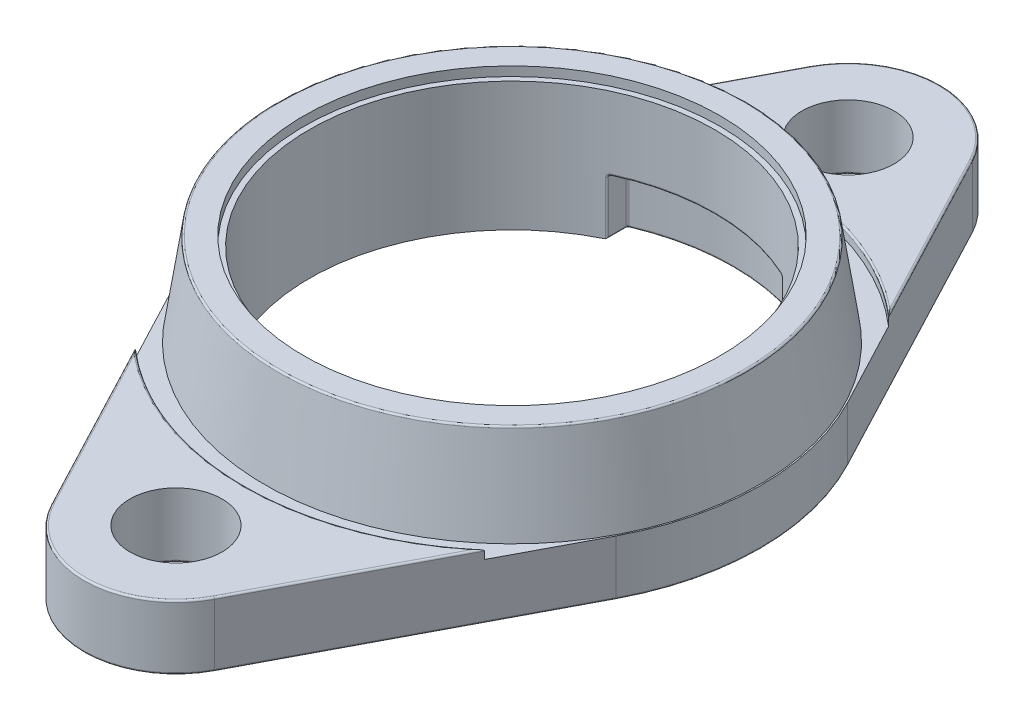
SolidWorks part; units mm, degrees
material "Zinco AC41A Liga, como fundido"
ref_plane "Plano frontal" through (0, 0, 0) normal (0, 0, 1) x (1, 0, 0)
ref_plane "Plano superior" through (0, 0, 0) normal (0, 1, 0) x (1, 0, 0)
ref_plane "Plano direito" through (0, 0, 0) normal (1, 0, 0) x (0, 0, -1)
sketch "Esboço3" plane through (0, 0, 0) normal (0, 1, 0) x (1, 0, 0)
  line L0 (-11.9463, 6.2877) -> (-4.4246, 20.5788)
  line L1 (4.4246, 20.5788) -> (11.9463, 6.2877)
  line L2 (-11.9463, -6.2877) -> (-4.4246, -20.5788)
  line L3 (4.4246, -20.5788) -> (11.9463, -6.2877)
  circle A0 centre (0, 0) radius 11
  arc A1 (-11.9463, 6.2877) -> (-11.9463, -6.2877) centre (0, 0) ccw
  arc A2 (-4.4246, 20.5788) -> (4.4246, 20.5788) centre (0, 18.25) cw
  arc A3 (-4.4246, -20.5788) -> (4.4246, -20.5788) centre (0, -18.25) ccw
  arc A4 (11.9463, -6.2877) -> (11.9463, 6.2877) centre (0, 0) ccw
  circle A5 centre (0, 18.25) radius 2.5
  circle A6 centre (0, -18.25) radius 2.5
  dimension "D1" = 22
  dimension "D2" = 27
  dimension "D4" = 46.5
  dimension "D3" = 5
  dimension "D5" = 5
  dimension "D6" = 5
extrude "Ressalto-extrusão1" add sketch "Esboço3" along normal blind 3
sketch "Esboço4" plane through (0, 0, 0) normal (1, 0, 0) x (0, 0, -1)
  line L0 (0, 0) -> (0, 3) construction
  line L1 (6.2877, 3) -> (-6.2877, 3) construction
  line L2 (-11, 3) -> (-11, 7.5)
  line L3 (-11, 7.5) -> (-11.3, 7.5)
  line L4 (-11.3, 7.5) -> (-11.3, 8)
  line L5 (-11.3, 8) -> (-12.675, 8)
  line L6 (-12.675, 8) -> (-13.425, 3)
  line L7 (-20.5788, 3) -> (-6.2877, 3) construction
  line L8 (-13.425, 3) -> (-11, 3)
  dimension "D1" = 4.5
  dimension "D2" = 12.675
  dimension "D3" = 13.425
  dimension "D4" = 0.5
  dimension "D5" = 0.3
revolve "Revolução1" add sketch "Esboço4" angle 360 about L0
sketch "Esboço6" plane through (0, 3, 0) normal (0, 1, 0) x (1, 0, 0)
  line L0 (-9.4818, 10.9702) -> (-4.4246, 20.5788)
  line L1 (-4.4246, 20.5788) -> (-11.9463, 6.2877) construction
  line L2 (4.4246, 20.5788) -> (9.4818, 10.9702)
  line L3 (11.9463, 6.2877) -> (4.4246, 20.5788) construction
  line L4 (-9.4818, -10.9702) -> (-4.4246, -20.5788)
  line L5 (-11.9463, -6.2877) -> (-4.4246, -20.5788) construction
  line L6 (4.4246, -20.5788) -> (9.4818, -10.9702)
  line L7 (4.4246, -20.5788) -> (11.9463, -6.2877) construction
  arc A0 (-4.4246, 20.5788) -> (4.4246, 20.5788) centre (0, 18.25) cw
  arc A1 (-4.4246, -20.5788) -> (4.4246, -20.5788) centre (0, -18.25) ccw
  arc A2 (-9.4818, -10.9702) -> (9.4818, -10.9702) centre (0, 0) ccw
  arc A3 (9.4818, 10.9702) -> (-9.4818, 10.9702) centre (0, 0) ccw
  dimension "D1" = 29
extrude "Ressalto-extrusão2" add sketch "Esboço6" along normal blind 0.5
sketch "Esboço7" plane through (0, 0, 0) normal (0, -1, 0) x (1, 0, 0)
  line L11 (-2.876, -19.7637) -> (-10.3977, -5.4726)
  line L12 (-10.3977, 5.4726) -> (-2.876, 19.7637)
  line L13 (-4.3256, -17.0094) -> (-10.3977, -5.4726)
  line L14 (-10.3977, 5.4726) -> (-4.3256, 17.0094)
  line L19 (10.3977, -5.4726) -> (2.876, -19.7637)
  line L20 (2.876, 19.7637) -> (10.3977, 5.4726)
  line L21 (10.3977, -5.4726) -> (4.3256, -17.0094)
  line L22 (4.3256, 17.0094) -> (10.3977, 5.4726)
  arc A5 (-10.3977, 5.4726) -> (-10.3977, -5.4726) centre (0, 0) ccw
  arc A6 (-10.3977, 5.4726) -> (-10.3977, -5.4726) centre (0, 0) ccw
  arc A8 (4.3256, -17.0094) -> (-4.3256, -17.0094) centre (0, -18.25) ccw
  arc A9 (10.3977, -5.4726) -> (10.3977, 5.4726) centre (0, 0) ccw
  arc A10 (10.3977, -5.4726) -> (10.3977, 5.4726) centre (0, 0) ccw
  arc A11 (-4.3256, 17.0094) -> (4.3256, 17.0094) centre (0, 18.25) ccw
  dimension "D3" = 9
  dimension "D1" = 1.75
  dimension "D2" = 1.75
extrude "Corte-extrusão1" cut sketch "Esboço7" against normal blind 0.5
sketch "Esboço8" plane through (0, 0.5, 0) normal (0, -1, 0) x (1, 0, 0)
  line L0 (-4.75, 11.0199) -> (-4.75, 9.9216)
  line L1 (4.75, 11.0199) -> (4.75, 9.9216)
  line L2 (0, 0) -> (0, -15.75) construction
  line L3 (-4.75, -9.9216) -> (-4.75, -11.0199)
  line L4 (4.75, -9.9216) -> (4.75, -11.0199)
  arc A0 (-4.75, -11.0199) -> (4.75, -11.0199) centre (0, 0) ccw
  circle A3 centre (0, 0) radius 11 construction
  circle A4 centre (0, -18.25) radius 2.5 construction
  arc A5 (-4.75, -9.9216) -> (4.75, -9.9216) centre (0, 0) ccw
  arc A6 (4.75, 9.9216) -> (-4.75, 9.9216) centre (0, 0) ccw
  arc A7 (4.75, 11.0199) -> (-4.75, 11.0199) centre (0, 0) ccw
  dimension "D1" = 1
  dimension "D2" = 9.5
extrude "Corte-extrusão2" cut sketch "Esboço8" against normal blind 3
fillet "Filete1" radius 0.1 48 edges at (4.75, 0.5, -10.4707) (4.75, 2, -9.9216) (4.75, 0.5, 10.4707) (-4.75, 2, -11.0199) (4.75, 2, -11.0199) (0, 0.5, -12) (-4.75, 3.5, -10.4707) (0, 3.5, -11) (4.75, 3.5, -10.4707) (0, 3.5, -12) (0, 0, 20.75) (-8.1855, 0, 13.4332) (0, 0, 23.25) (8.1855, 0, 13.4332) (13.5, 0, 0) (8.1855, 0, -13.4332) (0, 0, -23.25) (-8.1855, 0, -13.4332) (-13.5, 0, 0) (0, 0, -15.75) (0, 0, 13.75) (-7.3617, 0, 11.241) (-11.75, 0, 0) (-7.3617, 0, -11.241) (0, 0, -13.75) (7.3617, 0, -11.241) (11.75, 0, 0) (7.3617, 0, 11.241) (6.9532, 3.5, 15.7745) (0, 3.5, 23.25) (-6.9532, 3.5, 15.7745) (0, 3.5, 14.5) (-6.9532, 3.5, -15.7745) (0, 3.5, -23.25) (6.9532, 3.5, -15.7745) (0, 3.5, -14.5) (-4.75, 0.5, -10.4707) (-4.75, 2, -9.9216) (4.75, 2, 11.0199) (4.75, 3.5, 10.4707) (0, 0.5, 12) (-4.75, 0.5, 10.4707) (-4.75, 3.5, 10.4707) (0, 3.5, 12) (4.75, 2, 9.9216) (0, 3.5, 11) (-4.75, 2, 9.9216) (0, 8, -12.675)
hole_wizard "Furo de diâmetro Ø5.0 (5)1" positions "3DSketch1" profile "Esboço9" hole size "Ø5.0" standard "ISO"
sketch3d "3DSketch1"
  arc A2 (4.3361, 3.5, -20.5322) -> (-4.3361, 3.5, -20.5322) centre (0, 3.5, -18.25) ccw construction
  arc A3 (-4.3361, 3.5, 20.5322) -> (4.3361, 3.5, 20.5322) centre (0, 3.5, 18.25) ccw construction
  point P0 (0, 3.5, -18.25)
  point P2 (0, 3.5, 18.25)
  point P17 (0, 8.4, -18.25)
  point P23 (0, 8.4, 18.25)
sketch "Esboço9" plane through (0, 3.5, -18.25) normal (1, 0, 0) x (0, 0, 1)
  line L0 (0, 0) -> (0, 12.8522)
  line L1 (0, 12.8522) -> (2.5, 11.35)
  line L2 (2.5, 11.35) -> (2.5, 0)
  line L5 (2.5, 0) -> (0, 0)
  line L10 (0, 12.8522) -> (-2.5, 11.35) construction
  line L11 (0, -6.35) -> (0, 107.95) construction
  dimension "Hole Dia." = 5
  dimension "Hole Depth" = 11.35
  dimension "Drill Angle" = 118
